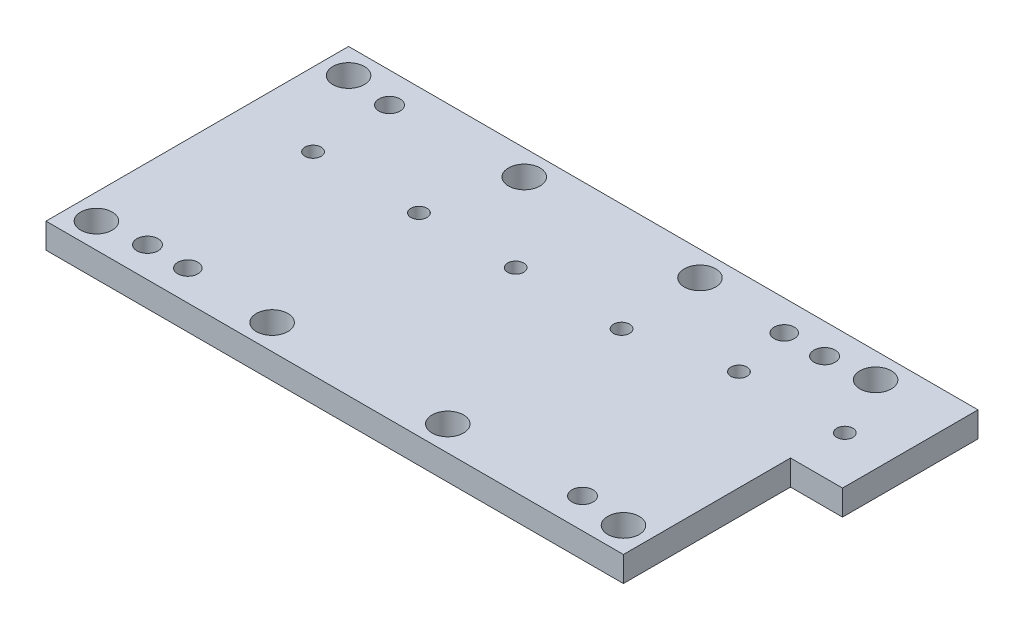
SolidWorks part; units mm, degrees
material "K110"
ref_plane "Front Plane" through (0, 0, 0) normal (0, 0, 1) x (1, 0, 0)
ref_plane "Top Plane" through (0, 0, 0) normal (0, 1, 0) x (1, 0, 0)
ref_plane "Right Plane" through (0, 0, 0) normal (1, 0, 0) x (0, 0, -1)
sketch "Sketch1" plane through (0, 0, 0) normal (0, 1, 0) x (1, 0, 0)
  line L0 (-229, 15.28) -> (-229, 9.28) construction
  line L1 (-229, -60) -> (0, -60)
  line L2 (-229, -60) -> (-229, 60)
  line L3 (-229, 60) -> (0, 60)
  line L4 (0, -60) -> (0, 60)
  point P0 (0, 0)
  dimension "D1" = 120
  dimension "D2" = 229
extrude "Boss-Extrude1" add sketch "Sketch1" against normal blind 10
sketch "Sketch2" plane through (0, 0, 0) normal (0, 1, 0) x (1, 0, 0)
  line L0 (21.6325, 5.27) -> (21.6325, 60) construction
  line L1 (0, 60) -> (20.6325, 60)
  line L2 (0, 60) -> (0, 6.27)
  line L3 (0, 6.27) -> (20.6325, 6.27)
  line L4 (20.6325, 60) -> (20.6325, 6.27)
  line L5 (1, 5.27) -> (21.6325, 5.27) construction
  dimension "D1" = 1
  dimension "D2" = 1
extrude "Boss-Extrude2" add sketch "Sketch2" against normal up to surface (10 mm away) up to face at (-114.5, -10, 0)
hole_wizard "Ø12.5 (12.5) Diameter Hole1" positions "Sketch5" profile "Sketch4" hole size "Ø12.5" standard "ISO" end condition through all
sketch "Sketch5" plane through (0, -10, 0) normal (0, -1, 0) x (-1, 0, 0)
  line L0 (80.2527, 48.6977) -> (79.3713, 51.6698) construction
  point P0 (9.969, 50)
  point P3 (79.812, 50.1838)
  point P7 (149.323, 50)
  point P10 (219, 50)
  point P13 (219, -50)
  point P16 (149.323, -50)
  point P19 (79.646, -50)
  point P22 (9.969, -50)
sketch "Sketch4" plane through (-9.969, -10, -50) normal (1, 0, 0) x (0, 0, -1)
  line L0 (0, 0) -> (0, 10)
  line L1 (0, 10) -> (6.25, 10)
  line L2 (6.25, 10) -> (6.25, 0)
  line L5 (6.25, 0) -> (0, 0)
  line L11 (0, -6.35) -> (0, 107.95) construction
  dimension "Thru Hole Dia." = 12.5
  dimension "Thru Hole Depth" = 10
hole_wizard "M6 Clearance Hole1" positions "Sketch8" profile "Sketch7" hole size "M6" standard "ISO" end condition through all
sketch "Sketch8" plane through (0, -10, 0) normal (0, -1, 0) x (-1, 0, 0)
  point P0 (-2.125, 25.691)
  point P3 (39.875, 25.691)
  point P6 (77.875, 17.1524)
  point P9 (119.875, 17.1524)
  point P12 (157.875, 16.78)
  point P15 (199.875, 16.78)
sketch "Sketch7" plane through (2.125, -10, -25.691) normal (1, 0, 0) x (0, 0, -1)
  line L0 (0, 0) -> (0, 10)
  line L1 (0, 10) -> (3.2, 10)
  line L2 (3.2, 10) -> (3.2, 0)
  line L5 (3.2, 0) -> (0, 0)
  line L11 (0, -6.35) -> (0, 107.95) construction
  dimension "Thru Hole Dia." = 6.4
  dimension "Thru Hole Depth" = 10
hole_wizard "Ø8.0mm Dowel Hole1" positions "Sketch11" profile "Sketch10" hole size "Ø8.0" standard "ISO" end condition through all
sketch "Sketch11" plane through (0, -10, 0) normal (0, -1, 0) x (-1, 0, 0)
  point P1 (184.75, -48)
  point P4 (44.219, 48)
sketch "Sketch10" plane through (-184.75, -10, 48) normal (1, 0, 0) x (0, 0, -1)
  line L0 (0, 0) -> (0, 10)
  line L1 (0, 10) -> (4, 10)
  line L2 (4, 10) -> (4, 0)
  line L5 (4, 0) -> (0, 0)
  line L11 (0, -6.35) -> (0, 107.95) construction
  dimension "Thru Hole Dia." = 8
  dimension "Thru Hole Depth" = 10
hole_wizard "M8 Clearance Hole1" positions "Sketch14" profile "Sketch13" hole size "M8" standard "ISO" end condition through all
sketch "Sketch14" plane through (0, -10, 0) normal (0, -1, 0) x (-1, 0, 0)
  point P0 (28.219, 48)
  point P3 (200.75, 48)
  point P6 (200.75, -48)
  point P9 (28.219, -48)
sketch "Sketch13" plane through (-28.219, -10, -48) normal (1, 0, 0) x (0, 0, -1)
  line L0 (0, 0) -> (0, 10)
  line L1 (0, 10) -> (4.2, 10)
  line L2 (4.2, 10) -> (4.2, 0)
  line L5 (4.2, 0) -> (0, 0)
  line L11 (0, -6.35) -> (0, 107.95) construction
  dimension "Thru Hole Dia." = 8.4
  dimension "Thru Hole Depth" = 10
